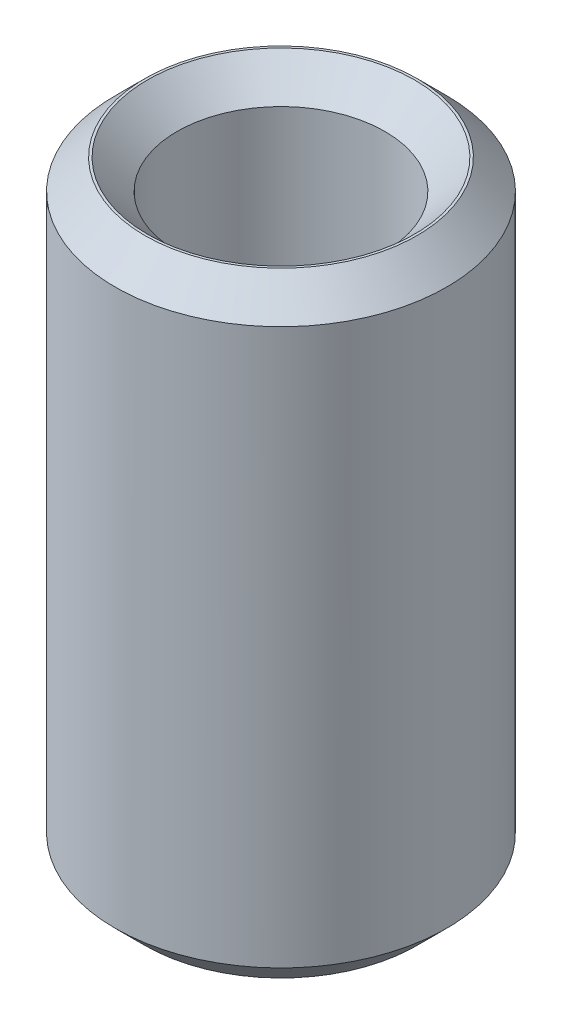
SolidWorks part; units mm, degrees
ref_plane "Front Plane" through (0, 0, 0) normal (0, 0, 1) x (1, 0, 0)
ref_plane "Top Plane" through (0, 0, 0) normal (0, 1, 0) x (1, 0, 0)
ref_plane "Right Plane" through (0, 0, 0) normal (1, 0, 0) x (0, 0, -1)
sketch "Sketch1" plane through (0, 0, 0) normal (0, 1, 0) x (1, 0, 0)
  circle A0 centre (0, 0) radius 15
  dimension "SLEEVE_OD" = 30
extrude "Boss-Extrude1" add sketch "Sketch1" along normal blind 55.6229
sketch "Sketch2" plane through (0, 0, 0) normal (0, 1, 0) x (1, 0, 0)
  circle A0 centre (0, 0) radius 9.4018
  dimension "BORE_D" = 18.8035
extrude "Cut-Extrude1" cut sketch "Sketch2" along normal through all
chamfer "Chamfer1" distance 2.6882 angle 45 4 edges at (0, 55.6229, 9.4018) (0, 0, 9.4018) (0, 0, 15) (0, 55.6229, 15)
